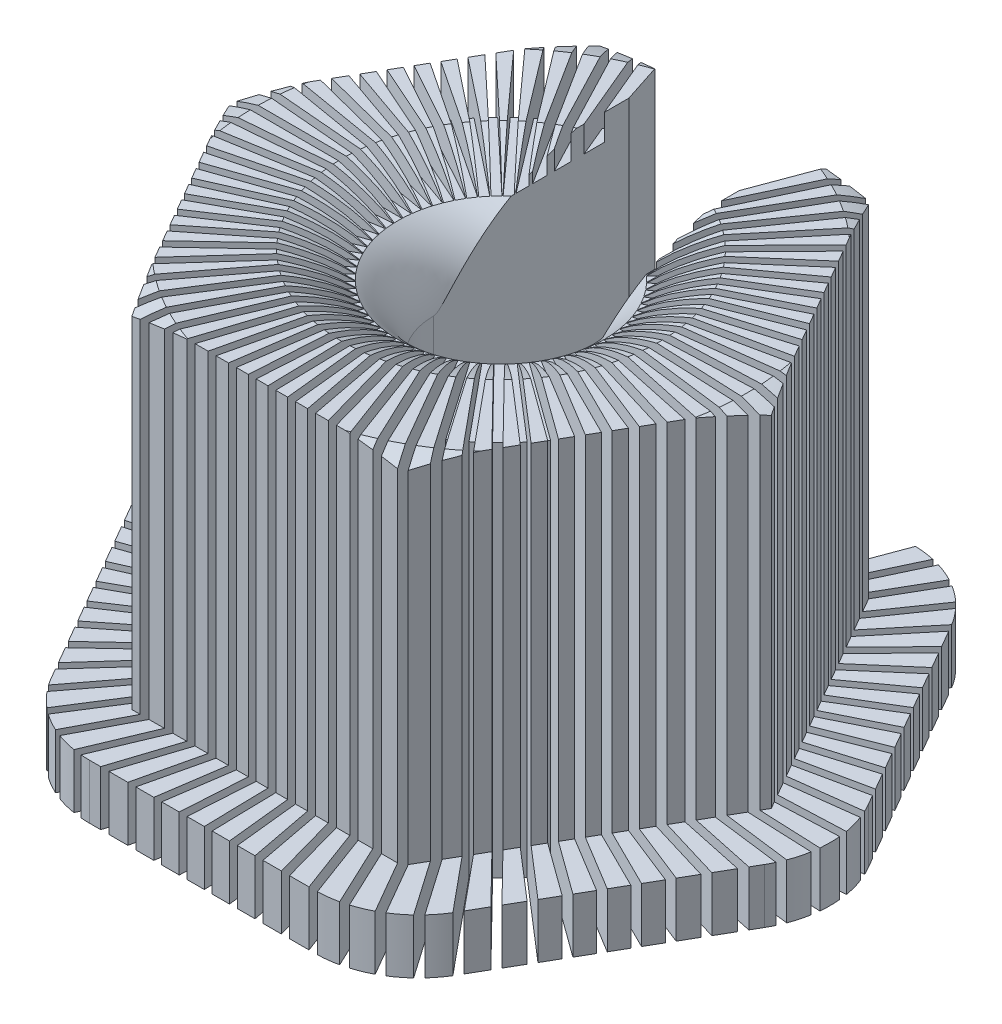
SolidWorks part; units mm, degrees
ref_plane "Front Plane" through (0, 0, 0) normal (0, 0, 1) x (1, 0, 0)
ref_plane "Top Plane" through (0, 0, 0) normal (0, 1, 0) x (1, 0, 0)
ref_plane "Right Plane" through (0, 0, 0) normal (1, 0, 0) x (0, 0, -1)
sketch "Sketch1" plane through (0, 0, 0) normal (0, 1, 0) x (1, 0, 0)
  line L1 (60.6218, 10) -> (38.9711, 47.5)
  line L2 (21.6506, 57.5) -> (-21.6506, 57.5)
  line L3 (-38.9711, 47.5) -> (-60.6218, 10)
  line L4 (-60.6218, -10) -> (-38.9711, -47.5)
  line L5 (-21.6506, -57.5) -> (21.6506, -57.5)
  line L6 (38.9711, -47.5) -> (60.6218, -10)
  circle A0 centre (0, 0) radius 57.5 construction
  arc A1 (-21.6506, -57.5) -> (-38.9711, -47.5) centre (-21.6506, -37.5) cw
  arc A2 (21.6506, -57.5) -> (38.9711, -47.5) centre (21.6506, -37.5) ccw
  arc A3 (60.6218, -10) -> (60.6218, 10) centre (43.3013, 0) ccw
  arc A4 (38.9711, 47.5) -> (21.6506, 57.5) centre (21.6506, 37.5) ccw
  arc A5 (-21.6506, 57.5) -> (-38.9711, 47.5) centre (-21.6506, 37.5) ccw
  arc A6 (-60.6218, -10) -> (-60.6218, 10) centre (-43.3013, 0) cw
  dimension "D1" = 115
  dimension "D2" = 20
extrude "Boss-Extrude2" add sketch "Sketch1" along normal blind 77.5
sketch "Sketch6" plane through (0, 77.5, 0) normal (0, 1, 0) x (1, 0, 0)
  circle A0 centre (0, 0) radius 13
extrude "Cut-Extrude1" cut sketch "Sketch6" against normal up to surface (77.5 mm away) up to face at (0, 0, 0)
sketch "Sketch7" plane through (0, 0, 0) normal (0, 0, 1) x (1, 0, 0)
  line L0 (0, 77.5) -> (0, 0) construction
  line L1 (-21.6506, 77.5) -> (21.6506, 77.5) construction
  line L2 (0, 77.5) -> (13, 77.5) construction
  line L3 (13, 77.5) -> (13, 60)
  line L4 (13, 77.5) -> (30.5, 77.5)
  line L5 (38.9711, 77.5) -> (21.6506, 77.5) construction
  line L6 (13, 0) -> (63.3013, 0) construction
  line L7 (38.9711, 0) -> (38.9711, 77.5) construction
  line L8 (64.9423, 77.5) -> (47.4423, 77.5)
  line L9 (64.9423, 77.5) -> (64.9423, 60)
  line L10 (13, 77.5) -> (-13, 77.5) construction
  line L11 (13, 77.5) -> (18.5176, 71.4317) construction
  spline S0 degree 2 poles (13, 60) (14.0037, 72.8919) (30.5, 77.5) knots 0 0 0 1 1 1
  spline S1 degree 2 poles (64.9423, 60) (63.9386, 72.8919) (47.4423, 77.5) knots 0 0 0 1 1 1
  dimension "D1" = 13
  dimension "D2" = 17.5
  dimension "D3" = 17.5
  dimension "D4" = 8.2017
revolve "Cut-Revolve1" cut sketch "Sketch7" angle 360 about L0
ref_plane "Plane1" through (0, 38.75, 0) normal (0, 1, 0) x (1, 0, 0)
sketch "Sketch8" plane through (0, 0, 0) normal (0, 0, 1) x (1, 0, 0)
  line L0 (-63.3013, 77.5) -> (-63.3013, 0)
  line L1 (-13.3013, 5) -> (-38.3013, 5) construction
  line L2 (-38.3013, 5) -> (-38.3013, 0)
  line L3 (-63.3013, 0) -> (-38.3013, 0)
  line L4 (-13.3013, 0) -> (-13.3013, 5) construction
  line L5 (-38.3013, 5) -> (-38.3013, 72.5)
  line L6 (63.25, 38.75) -> (-63.25, 38.75) construction
  line L7 (-63.3013, 38.75) -> (-38.3013, 38.75) construction
  line L8 (-13.3013, 77.5) -> (-13.3013, 72.5)
  line L9 (-63.3013, 77.5) -> (-13.3013, 77.5)
  line L10 (-13.3013, 72.5) -> (-38.3013, 72.5)
  line L11 (-38.3013, 0) -> (-13.3013, 0) construction
  point P3 (-66.188, 24)
  dimension "D1" = 50
  dimension "D2" = 50
  dimension "D3" = 5
  dimension "D4" = 25
extrude "Cut-Extrude2" cut sketch "Sketch8" against normal blind 0.75 and the other way blind 0.75
pattern_circular "CirPattern1" count 75 over 360 about axis through (0, -36.7696, 0) along (0, 1, 0) of "Cut-Extrude2"
sketch "Sketch9" plane through (0, 77.5, 0) normal (0, 1, 0) x (1, 0, 0)
  line L1 (51.9615, 0) -> (25.9808, 45)
  line L2 (25.9808, 45) -> (-25.9808, 45)
  line L3 (-25.9808, 45) -> (-51.9615, 0)
  line L4 (-51.9615, 0) -> (-25.9808, -45)
  line L5 (-25.9808, -45) -> (25.9808, -45)
  line L6 (25.9808, -45) -> (51.9615, 0)
  circle A0 centre (0, 0) radius 45 construction
  dimension "D1" = 90
extrude "Cut-Extrude3" cut sketch "Sketch9" against normal blind 67 flip side to cut
sketch "Sketch11" plane through (0, 0, 0) normal (0, -1, 0) x (1, 0, 0)
  line L0 (13, 0) -> (-13, 0) construction
  line L1 (-13, 0) -> (13, 0)
  line L2 (-13, 0) -> (-13, -62.1427)
  line L3 (13, 0) -> (13, -62.1427)
  line L4 (-13, -62.1427) -> (13, -62.1427)
  circle A0 centre (0, 0) radius 13 construction
  point P7 (0, 0)
extrude "Cut-Extrude6" cut sketch "Sketch11" against normal through all
